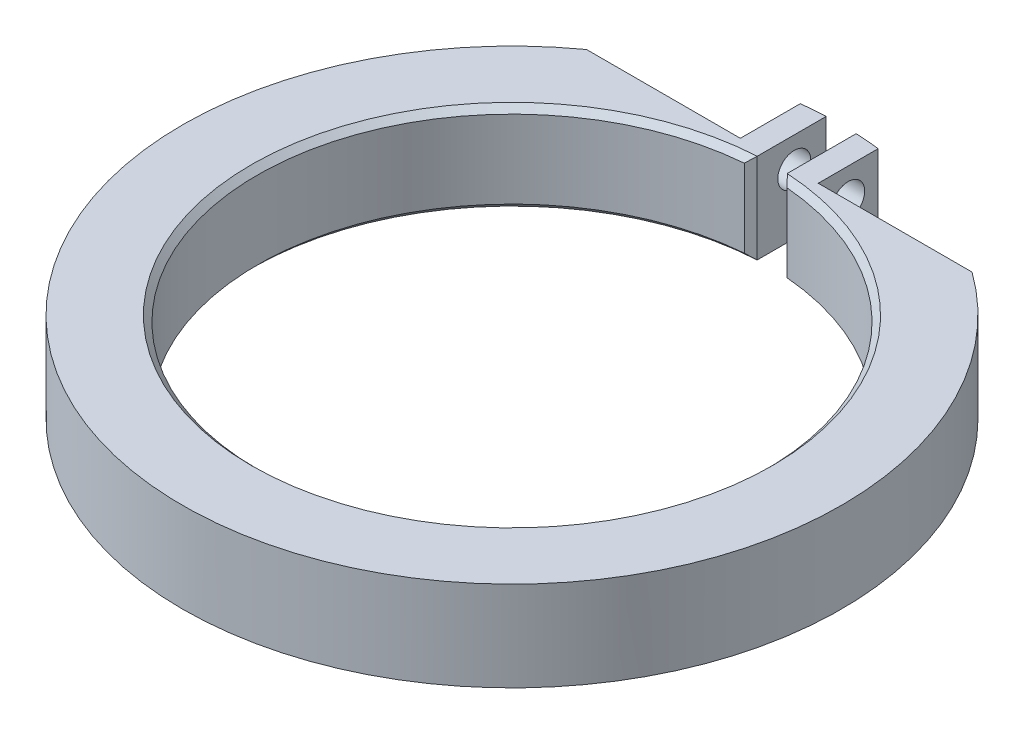
SolidWorks part; units mm, degrees
material "1.0060 (E335)"
ref_plane "Front Plane" through (0, 0, 0) normal (0, 0, 1) x (1, 0, 0)
ref_plane "Top Plane" through (0, 0, 0) normal (0, 1, 0) x (1, 0, 0)
ref_plane "Right Plane" through (0, 0, 0) normal (1, 0, 0) x (0, 0, -1)
sketch "Sketch1" plane through (0, 0, 0) normal (0, 1, 0) x (1, 0, 0)
  circle A0 centre (0, 0) radius 42.5
  circle A1 centre (0, 0) radius 55
  dimension "D1" = 85
  dimension "D2" = 110
extrude "Boss-Extrude1" add sketch "Sketch1" along normal blind 15
sketch "Sketch2" plane through (0, 15, 0) normal (0, 1, 0) x (1, 0, 0)
  line L0 (0, -1000) -> (0, 49000) construction
  line L1 (-2.5, 42.4264) -> (-2.5, 54.9432)
  line L2 (2.5, 42.4264) -> (2.5, 54.9432)
  circle A0 centre (0, 0) radius 42.5 construction
  circle A1 centre (0, 0) radius 55 construction
  arc A2 (2.5, 42.4264) -> (-2.5, 42.4264) centre (0, 0) ccw
  arc A3 (2.5, 54.9432) -> (-2.5, 54.9432) centre (0, 0) ccw
  dimension "D1" = 5
extrude "Cut-Extrude1" cut sketch "Sketch2" against normal through all
sketch "Sketch3" plane through (0, 15, 0) normal (0, 1, 0) x (1, 0, 0)
  line L0 (-6.5, 54.6146) -> (-6.5, 44.6146)
  line L1 (-6.5, 44.6146) -> (-32.1643, 44.6146)
  line L3 (-2.5, 54.9432) -> (-2.5, 42.4264) construction
  line L4 (0, -1000) -> (0, 49000) construction
  line L5 (6.5, 44.6146) -> (32.1643, 44.6146)
  line L6 (6.5, 54.6146) -> (6.5, 44.6146)
  arc A0 (-2.5, 54.9432) -> (2.5, 54.9432) centre (0, 0) ccw construction
  arc A1 (-6.5, 54.6146) -> (-32.1643, 44.6146) centre (0, 0) ccw
  arc A3 (6.5, 54.6146) -> (32.1643, 44.6146) centre (0, 0) cw
  dimension "D1" = 10
  dimension "D2" = 4
extrude "Cut-Extrude2" cut sketch "Sketch3" against normal blind 10
sketch "Sketch4" plane through (-6.5, 0, 0) normal (-1, 0, 0) x (0, 0, 1)
  line L0 (-44.6146, 15) -> (-54.6146, 15) construction
  line L1 (-54.6146, 5) -> (-54.6146, 15) construction
  circle A0 centre (-49.6146, 10) radius 2.75
  point P2 (-49.6146, 15)
  point P6 (-54.6146, 10)
  dimension "D1" = 5.5
extrude "Cut-Extrude3" cut sketch "Sketch4" against normal through all
fillet "Fillet2" radius 2 2 edges at (-19.3321, 5, -44.6146) (19.3321, 5, -44.6146)
chamfer "Chamfer1" distance 1 angle 45 4 edges at (0, 0, 42.5) (2.5, 7.5, -42.4264) (0, 15, 42.5) (-2.5, 7.5, -42.4264)
